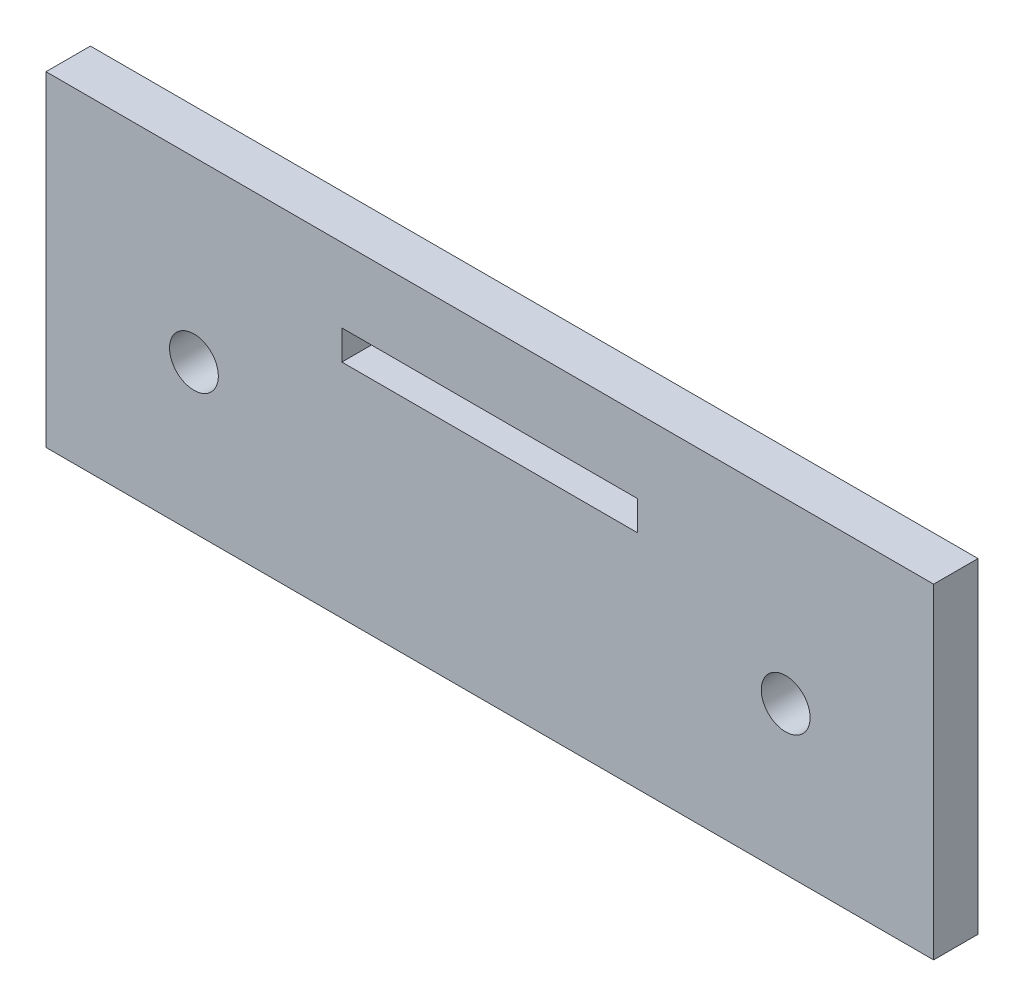
SolidWorks part; units mm, degrees
ref_plane "前视基准面" through (0, 0, 0) normal (0, 0, 1) x (1, 0, 0)
ref_plane "上视基准面" through (0, 0, 0) normal (0, 1, 0) x (1, 0, 0)
ref_plane "右视基准面" through (0, 0, 0) normal (1, 0, 0) x (0, 0, -1)
other "Configuration Table"
sketch "草图2" plane through (0, 0, 0) normal (0, 0, 1) x (1, 0, 0)
  line L1 (0, 0) -> (60, 0)
  line L2 (0, 0) -> (0, 22)
  line L3 (0, 22) -> (60, 22)
  line L4 (60, 0) -> (60, 22)
  dimension "D1" = 22
  dimension "D2" = 60
base flange "基体-法兰1" sketch "草图2" thickness 3 reverse thickness direction no parameters "D1"=0.7366
sketch "草图7" plane through (0, 0, 0) normal (0, 0, 1) x (1, 0, 0)
  line L1 (20, 17) -> (40, 17)
  line L2 (20, 17) -> (20, 15)
  line L3 (20, 15) -> (40, 15)
  line L4 (40, 17) -> (40, 15)
  line L5 (60, 22) -> (0, 22) construction
  line L6 (30, 22) -> (30, 0) construction
  line L7 (0, 0) -> (60, 0) construction
  line L8 (0, 11) -> (60, 11) construction
  line L9 (0, 22) -> (0, 0) construction
  line L10 (60, 0) -> (60, 22) construction
  line L11 (20, 22) -> (20, 0) construction
  line L12 (40, 22) -> (40, 0) construction
  line L13 (0, 15) -> (60, 15) construction
  dimension "D1" = 10
  dimension "D4" = 2
  dimension "D5" = 20
  dimension "D2" = 10
  dimension "D3" = 4
extrude "切除-拉伸1" cut sketch "草图7" against normal blind 30 normal cut yes
sketch "草图8" plane through (0, 0, 0) normal (0, 0, 1) x (1, 0, 0)
  line L0 (30, 22) -> (30, 0) construction
  line L1 (60, 22) -> (0, 22) construction
  line L2 (0, 0) -> (60, 0) construction
  line L3 (0, 11) -> (60, 11) construction
  line L4 (0, 22) -> (0, 0) construction
  line L5 (60, 0) -> (60, 22) construction
  line L6 (10, 22) -> (10, 0) construction
  line L7 (50, 22) -> (50, 0) construction
  line L8 (0, 10) -> (60, 10) construction
  line L9 (10, 10) -> (50, 10) construction
  circle A0 centre (10, 10) radius 1.65
  circle A1 centre (50, 10) radius 1.65
  dimension "D1" = 2
  dimension "D2" = 20
  dimension "D5" = 3.3
  dimension "D6" = 40
  dimension "D3" = 20
  dimension "D4" = 1
extrude "切除-拉伸2" cut sketch "草图8" against normal blind 10 contours A0 | A1 normal cut yes
sketch "折弯-线1" plane through (0, 0, 0) normal (0, 1, 0) x (1, 0, 0)
sketch "边界框1" plane through (0, 0, 0) normal (0, 1, 0) x (1, 0, 0)
sheet metal parameters "钣金11" thickness 3 parameters "D1"=0.7366
flat pattern "平板型式11" [suppressed]
sketch "折弯-线2" plane through (0, 0, 0) normal (0, 1, 0) x (1, 0, 0)
sketch "边界框2" [suppressed] plane through (0, 0, 0) normal (0, 1, 0) x (1, 0, 0)
sheet metal parameters "钣金12" thickness 3 parameters "D1"=0.7366
flat pattern "平板型式11"
sketch "折弯-线2" plane through (0, 0, 0) normal (0, 1, 0) x (1, 0, 0)
sketch "边界框2" [suppressed] plane through (0, 0, 0) normal (0, 1, 0) x (1, 0, 0)
sheet metal parameters "钣金25" thickness 3 parameters "D1"=0.7366
flat pattern "平板型式11"
sketch "折弯-线2" plane through (0, 0, 0) normal (0, 1, 0) x (1, 0, 0)
sketch "边界框2" [suppressed] plane through (0, 0, 0) normal (0, 1, 0) x (1, 0, 0)
